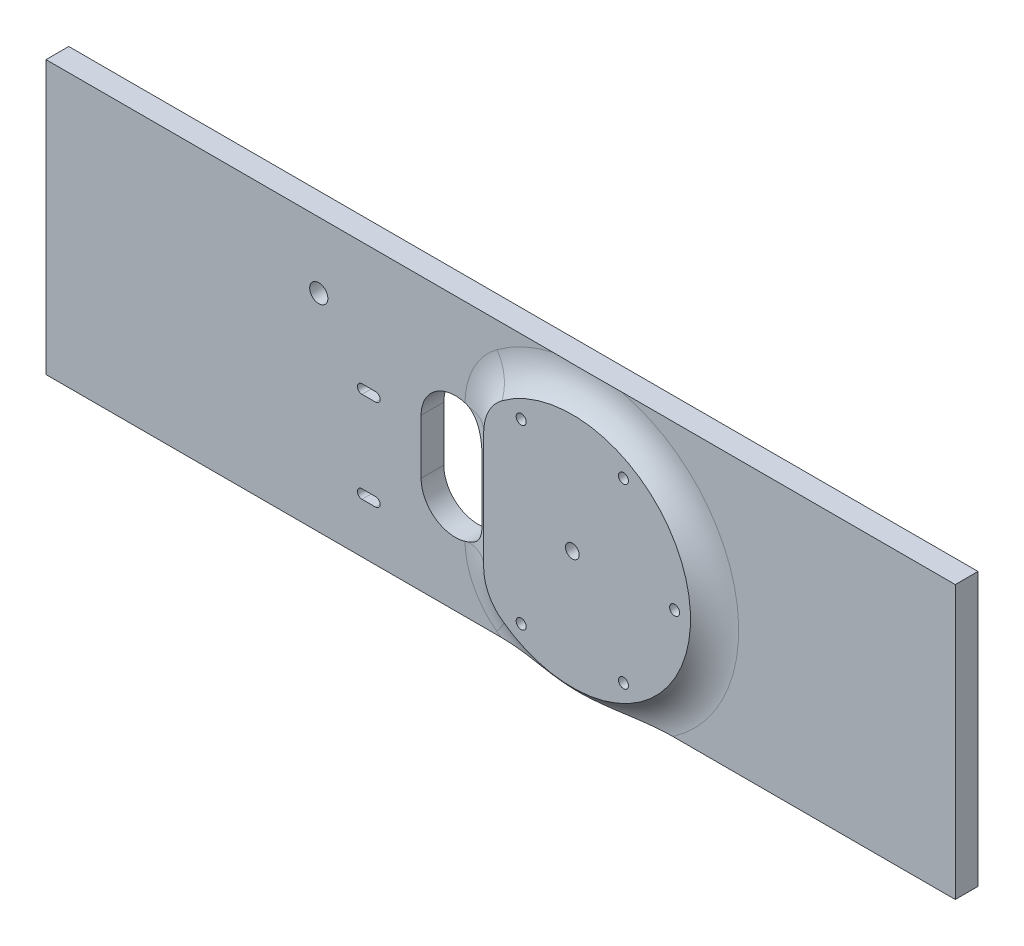
SolidWorks part; units mm, degrees
ref_plane "Front Plane" through (0, 0, 0) normal (0, 0, 1) x (1, 0, 0)
ref_plane "Top Plane" through (0, 0, 0) normal (0, 1, 0) x (1, 0, 0)
ref_plane "Right Plane" through (0, 0, 0) normal (1, 0, 0) x (0, 0, -1)
sketch "Sketch1" plane through (0, 0, 0) normal (0, 0, 1) x (1, 0, 0)
  line L0 (90, 33.5) -> (90, 21.5) construction
  line L1 (0, 0) -> (200, 0)
  line L2 (0, 0) -> (0, 60)
  line L3 (0, 60) -> (200, 60)
  line L4 (200, 0) -> (200, 60)
  line L5 (97.5, 33.5) -> (97.5, 21.5)
  line L6 (82.5, 33.5) -> (82.5, 21.5)
  line L7 (90, 27.5) -> (119, 27.5) construction
  circle A0 centre (119, 27.5) radius 26.5 construction
  circle A2 centre (119, 27.5) radius 1.5
  circle A3 centre (60, 45.5) radius 2
  arc A4 (97.5, 33.5) -> (82.5, 33.5) centre (90, 33.5) ccw
  arc A5 (82.5, 21.5) -> (97.5, 21.5) centre (90, 21.5) ccw
  arc A6 (142.525, 27.5) -> (140.475, 27.5) centre (141.5, 27.5) ccw construction
  arc A7 (129.225, 8.0144) -> (131.275, 8.0144) centre (130.25, 8.0144) ccw construction
  arc A8 (106.725, 8.0144) -> (108.775, 8.0144) centre (107.75, 8.0144) ccw construction
  arc A9 (106.725, 46.9856) -> (108.775, 46.9856) centre (107.75, 46.9856) ccw construction
  arc A10 (131.275, 46.9856) -> (129.225, 46.9856) centre (130.25, 46.9856) ccw construction
  arc A11 (142.525, 27.5) -> (140.475, 27.5) centre (141.5, 27.5) ccw construction
  arc A12 (129.225, 8.0144) -> (131.275, 8.0144) centre (130.25, 8.0144) ccw construction
  arc A13 (106.725, 8.0144) -> (108.775, 8.0144) centre (107.75, 8.0144) ccw construction
  arc A14 (106.725, 46.9856) -> (108.775, 46.9856) centre (107.75, 46.9856) ccw construction
  arc A15 (131.275, 46.9856) -> (129.225, 46.9856) centre (130.25, 46.9856) ccw construction
  circle A16 centre (130.25, 46.9856) radius 1.1
  circle A17 centre (141.5, 27.5) radius 1.1
  circle A18 centre (130.25, 8.0144) radius 1.1
  circle A19 centre (107.75, 8.0144) radius 1.1
  circle A20 centre (107.75, 46.9856) radius 1.1
  point P8 (90, 27.5)
  dimension "D1" = 3
  dimension "D2" = 4
  dimension "D5" = 53
  dimension "D9" = 1
  dimension "D12" = 5
  dimension "D13" = 2.2
  dimension "D3" = 59
  dimension "D4" = 18
  dimension "D6" = 60
  dimension "D7" = 200
  dimension "D8" = 60
  dimension "D10" = 12
  dimension "D11" = 15
extrude "Boss-Extrude1" add sketch "Sketch1" along normal blind 5
sketch "Sketch3" plane through (0, 0, 5) normal (0, 0, 1) x (1, 0, 0)
  line L0 (99.5, 40.3744) -> (99.5, 14.6256)
  line L1 (97.5, 21.5) -> (97.5, 33.5) construction
  arc A0 (103.5625, 6.5791) -> (103.5625, 48.4209) centre (119, 27.5) ccw
  arc A1 (99.5, 40.3744) -> (103.5625, 48.4209) centre (109.5, 40.3744) cw
  arc A2 (99.5, 14.6256) -> (103.5625, 6.5791) centre (109.5, 14.6256) ccw
  circle A3 centre (119, 27.5) radius 1.5 construction
  circle A4 centre (107.75, 8.0144) radius 1.1 construction
  circle A5 centre (130.25, 8.0144) radius 1.1 construction
  circle A6 centre (141.5, 27.5) radius 1.1 construction
  circle A7 centre (130.25, 46.9856) radius 1.1 construction
  circle A8 centre (107.75, 46.9856) radius 1.1 construction
  circle A9 centre (119, 27.5) radius 1.5
  circle A10 centre (107.75, 8.0144) radius 1.1
  circle A11 centre (130.25, 8.0144) radius 1.1
  circle A12 centre (141.5, 27.5) radius 1.1
  circle A13 centre (130.25, 46.9856) radius 1.1
  circle A14 centre (107.75, 46.9856) radius 1.1
  dimension "D1" = 10
  dimension "D3" = 26
  dimension "D2" = 2
extrude "Boss-Extrude2" add sketch "Sketch3" along normal up to surface (3.23 mm away)
fillet "Fillet1" radius 10 4 edges at (100.5732, 10.1187, 5) (99.5, 27.5, 5) (100.5732, 44.8813, 5) (145, 27.5, 5)
sketch "Sketch4" plane through (0, 0, 5) normal (0, 0, 1) x (1, 0, 0)
  line L0 (69.5, 32) -> (72.5, 32) construction
  line L1 (69.5, 33) -> (72.5, 33)
  line L2 (69.5, 31) -> (72.5, 31)
  line L3 (69.5, 12) -> (72.5, 12) construction
  line L4 (69.5, 13) -> (72.5, 13)
  line L5 (69.5, 11) -> (72.5, 11)
  line L6 (0, 0) -> (100.1154, 0) construction
  line L7 (82.5, 33.5) -> (82.5, 21.5) construction
  arc A0 (69.5, 33) -> (69.5, 31) centre (69.5, 32) ccw
  arc A1 (72.5, 31) -> (72.5, 33) centre (72.5, 32) ccw
  arc A2 (69.5, 13) -> (69.5, 11) centre (69.5, 12) ccw
  arc A3 (72.5, 11) -> (72.5, 13) centre (72.5, 12) ccw
  point P2 (71, 32)
  point P7 (71, 12)
  point P14 (0, 0)
  point P15 (65.2624, 31.7849)
  dimension "D1" = 3
  dimension "D2" = 20
  dimension "D3" = 12
  dimension "D4" = 10
  dimension "D5" = 2
extrude "Cut-Extrude1" cut sketch "Sketch4" against normal blind 10
